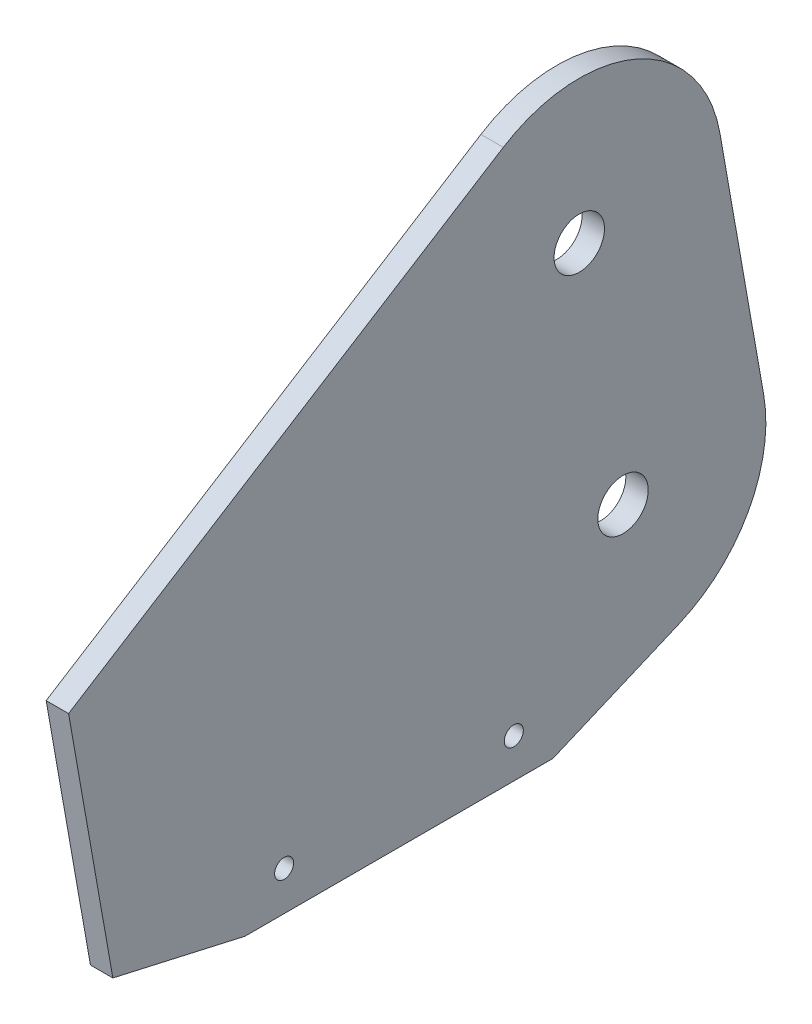
SolidWorks part; units mm, degrees
ref_plane "Front Plane" through (0, 0, 0) normal (0, 0, 1) x (1, 0, 0)
ref_plane "Top Plane" through (0, 0, 0) normal (0, 1, 0) x (1, 0, 0)
ref_plane "Right Plane" through (0, 0, 0) normal (1, 0, 0) x (0, 0, -1)
ref_plane "Plane1" through (-18, 0, 0) normal (-1, 0, 0) x (0, 0, 1)
sketch "Sketch2" plane through (-18, 0, 0) normal (-1, 0, 0) x (0, 0, 1)
  line L0 (51.0767, 42.3424) -> (58.9824, 87.178) construction
  line L1 (27.5, 37) -> (51.0767, 42.3424) construction
  line L4 (51.0767, 42.3424) -> (58.9824, 87.178)
  line L5 (-57.2984, 118.7444) -> (-65.1126, 74.428)
  line L6 (-49.9564, 46.5241) -> (-27.5, 37)
  line L7 (27.5, 37) -> (51.0767, 42.3424)
  line L8 (51.0767, 42.3424) -> (58.9824, 87.178)
  line L9 (58.9824, 87.178) -> (-18.6251, 135.9116)
  line L12 (27.5, 37) -> (51.0767, 42.3424)
  line L13 (51.0767, 42.3424) -> (58.9824, 87.178)
  line L14 (58.9824, 87.178) -> (-18.6251, 135.9116)
  line L15 (27.5, 37) -> (51.0767, 42.3424)
  line L17 (-27.5, 37) -> (27.5, 37)
  line L48 (-57.2984, 118.7444) -> (-65.1126, 74.428)
  line L50 (-49.9564, 46.5241) -> (-27.5, 37)
  line L51 (-27.5, 37) -> (27.5, 37)
  line L52 (-27.5, 37) -> (27.5, 37)
  arc A2 (-18.6251, 135.9116) -> (-57.2984, 118.7444) centre (-32.1858, 114.3163) ccw
  arc A8 (-18.6251, 135.9116) -> (-57.2984, 118.7444) centre (-32.1858, 114.3163) ccw construction
  arc A9 (-18.6251, 135.9116) -> (-57.2984, 118.7444) centre (-32.1858, 114.3163) ccw
  arc A20 (-65.1126, 74.428) -> (-49.9564, 46.5241) centre (-40, 70) ccw
  arc A21 (-65.1126, 74.428) -> (-49.9564, 46.5241) centre (-40, 70) ccw
  point P4 (0, 0)
  dimension "D1" = 0
extrude "Boss-Extrude1" add sketch "Sketch2" along normal blind 4 contours L12 L4 L14 region at (-18, 81.5947, -8.0864)
hole_wizard "Hole1" positions "Sketch3" profile "Sketch4" legacy end condition through all
sketch "Sketch3" plane through (-18, 0, 0) normal (1, 0, 0) x (0, 0, -1)
  point P0 (32.1858, 114.3163)
  point P3 (40, 70)
sketch "Sketch4" plane through (-18, 114.3163, -32.1858) normal (0, 1, 0) x (0, 0, -1)
  line L0 (0, 0) -> (0, 4)
  line L1 (0, 4) -> (4.5, 4)
  line L2 (4.5, 4) -> (4.5, 0)
  line L3 (4.5, 0) -> (0, 0)
  line L4 (0, 110) -> (0, -10) construction
  dimension "Diameter" = 9
  dimension "Depth" = 4
hole_wizard "M3 Clearance Hole1" positions "Sketch5" profile "Sketch6" hole size "M3" standard "ANSI Metric" end condition through all
sketch "Sketch5" plane through (-22, 0, 0) normal (-1, 0, 0) x (0, 0, 1)
  point P0 (20.5, 44)
  point P3 (-20.5, 44)
sketch "Sketch6" plane through (-22, 44, 20.5) normal (0, 1, 0) x (0, 0, 1)
  line L0 (0, 0) -> (0, 4)
  line L1 (0, 4) -> (1.7, 4)
  line L2 (1.7, 4) -> (1.7, 0.025)
  line L3 (1.7, 0.025) -> (1.725, 0)
  line L5 (1.725, 0) -> (0, 0)
  line L6 (-1.7, 0.025) -> (-1.725, 0) construction
  line L11 (0, -6.35) -> (0, 107.95) construction
  dimension "Thru Hole Dia." = 3.4
  dimension "Thru Hole Depth" = 4
  dimension "Near C'Sink Dia." = 3.45
  dimension "Near C'Sink Angle" = 90
